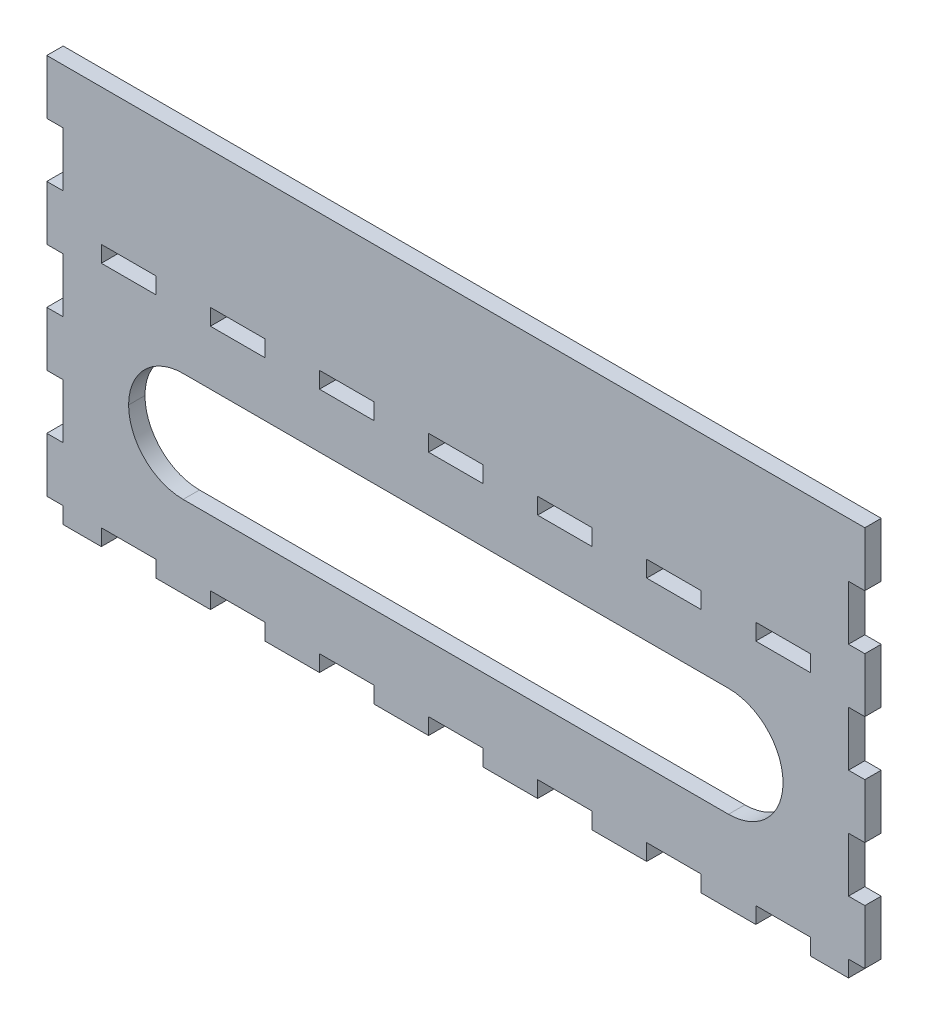
SolidWorks part; units mm, degrees
ref_plane "Front Plane" through (0, 0, 0) normal (0, 0, 1) x (1, 0, 0)
ref_plane "Top Plane" through (0, 0, 0) normal (0, 1, 0) x (1, 0, 0)
ref_plane "Right Plane" through (0, 0, 0) normal (1, 0, 0) x (0, 0, -1)
sketch "Sketch1" plane through (0, 0, 0) normal (0, 0, 1) x (1, 0, 0)
  line L1 (-75, -36.5) -> (75, -36.5)
  line L2 (-75, -36.5) -> (-75, 36.5)
  line L3 (-75, 36.5) -> (75, 36.5)
  line L4 (75, -36.5) -> (75, 36.5)
  line L5 (-75, -36.5) -> (75, 36.5) construction
  line L6 (-75, 36.5) -> (75, -36.5) construction
  point P0 (0, 0)
  dimension "D1" = 150
  dimension "D2" = 73
extrude "Boss-Extrude1" add sketch "Sketch1" along normal blind 3
sketch "Sketch2" plane through (0, 0, 3) normal (0, 0, 1) x (1, 0, 0)
  line L1 (-75, 36.5) -> (-75, -36.5) construction
  line L2 (-75, 26.5) -> (-72, 26.5)
  line L3 (-75, 26.5) -> (-75, 16.5)
  line L4 (-75, 16.5) -> (-72, 16.5)
  line L7 (-72, 26.5) -> (-72, 16.5)
  line L8 (75, 36.5) -> (-75, 36.5) construction
  dimension "D1" = 10
  dimension "D2" = 10
  dimension "D3" = 3
extrude "Cut-Extrude1" cut sketch "Sketch2" against normal through all
pattern_linear "LPattern1" count 4 spacing 20 along (0, -1, 0) of "Cut-Extrude1"
mirror "Mirror3" about plane through (0, 0, 0) normal (1, 0, 0) of "LPattern1"
sketch "Sketch4" plane through (0, 0, 3) normal (0, 0, 1) x (1, 0, 0)
  line L0 (-72, -36.5) -> (72, -36.5) construction
  line L1 (55, -36.5) -> (65, -36.5)
  line L2 (55, -36.5) -> (55, -33.5)
  line L3 (55, -33.5) -> (65, -33.5)
  line L4 (65, -36.5) -> (65, -33.5)
  line L7 (75, -33.5) -> (75, -23.5) construction
  dimension "D1" = 10
  dimension "D2" = 3
  dimension "D3" = 10
extrude "Cut-Extrude3" cut sketch "Sketch4" against normal through all
pattern_linear "LPattern2" count 8 spacing 20 along (-1, 0, 0) of "Cut-Extrude3"
sketch "Sketch5" plane through (0, 0, 3) normal (0, 0, 1) x (1, 0, 0)
  line L0 (75, 36.5) -> (-75, 36.5) construction
  line L1 (-65, 11.5) -> (-55, 11.5)
  line L2 (-65, 11.5) -> (-65, 8.5)
  line L3 (-65, 8.5) -> (-55, 8.5)
  line L4 (-55, 11.5) -> (-55, 8.5)
  line L5 (-75, 16.5) -> (-75, 6.5) construction
  dimension "D1" = 10
  dimension "D2" = 3
  dimension "D3" = 25
  dimension "D4" = 10
extrude "Cut-Extrude4" cut sketch "Sketch5" against normal through all
pattern_linear "LPattern4" count 7 spacing 20 along (1, 0, 0) of "Cut-Extrude4"
sketch "Sketch6" plane through (0, 0, 3) normal (0, 0, 1) x (1, 0, 0)
  line L0 (-75, -3.5) -> (-75, -13.5) construction
  line L1 (-60, -1.5) -> (60, -1.5)
  line L2 (-60, -1.5) -> (-60, -21.5)
  line L3 (-60, -21.5) -> (60, -21.5)
  line L4 (60, -1.5) -> (60, -21.5)
  line L5 (75, -13.5) -> (75, -3.5) construction
  line L6 (-15, -36.5) -> (-5, -36.5) construction
  line L7 (-25, 8.5) -> (-15, 8.5) construction
  dimension "D1" = 15
  dimension "D2" = 15
  dimension "D3" = 15
  dimension "D4" = 10
extrude "Cut-Extrude5" cut sketch "Sketch6" against normal through all
fillet "Fillet1" radius 10 4 edges at (60, -1.5, 1.5) (60, -21.5, 1.5) (-60, -1.5, 1.5) (-60, -21.5, 1.5)
